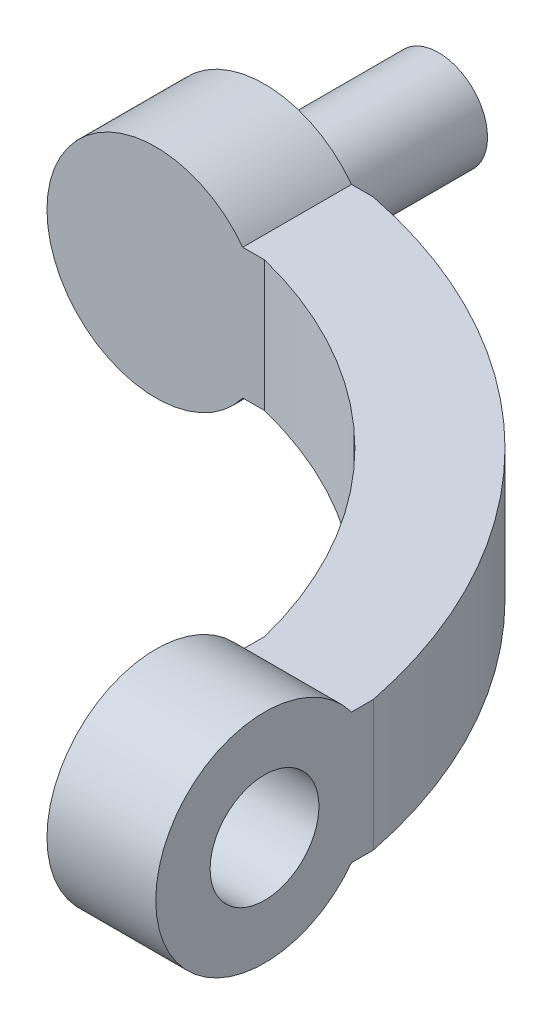
SolidWorks part; units mm, degrees
ref_plane "前视基准面" through (0, 0, 0) normal (0, 0, 1) x (1, 0, 0)
ref_plane "上视基准面" through (0, 0, 0) normal (0, 1, 0) x (1, 0, 0)
ref_plane "右视基准面" through (0, 0, 0) normal (1, 0, 0) x (0, 0, -1)
other "Configuration Table"
sketch "草图2" plane through (0, 0, 0) normal (0, 0, 1) x (1, 0, 0)
  circle A0 centre (0, 0) radius 5
  dimension "D1" = 10
extrude "凸台-拉伸3" add sketch "草图2" along normal blind 5
sketch "草图3" plane through (0, 0, 0) normal (0, 1, 0) x (1, 0, 0)
  line L0 (0, 0) -> (0, -25) construction
  line L1 (0, -25) -> (21.1976, -25) construction
  line L3 (0, 0) -> (5, 0)
  line L4 (0, 0) -> (0, -5)
  line L5 (0, -5) -> (5, -5)
  line L6 (5, 0) -> (5, -5)
  line L7 (20, -20) -> (25, -20)
  line L8 (20, -20) -> (20, -25)
  line L9 (20, -25) -> (25, -25)
  line L10 (25, -20) -> (25, -25)
  arc A0 (5, -5) -> (20, -20) centre (0, -25) cw
  arc A1 (5, 0) -> (25, -20) centre (0, -25) cw
  dimension "D1" = 20
  dimension "D2" = 5
  dimension "D3" = 5
extrude "凸台-拉伸4" add sketch "草图3" along normal blind 3 and the other way blind 3 separate body contours A1 L6 A0 L7 region at (15.52, 0, 9.48)
revolve "旋转1" add sketch "草图3<3>" angle 360 about L1 region at (22.5, 0, 22.5)
sketch "草图3<3>" plane through (0, 0, 0) normal (0, 1, 0) x (1, 0, 0) same geometry as "草图3"
sketch "草图4" plane through (0, 0, 20) normal (0, 0, 1) x (1, 0, 0)
  line L4 (25, 3) -> (20, 3)
  line L5 (20, 3) -> (20, -3)
  line L6 (20, -3) -> (25, -3)
  line L7 (25, -3) -> (25, 3)
  line L8 (25, 3) -> (20, 3)
  line L9 (20, 3) -> (20, -3)
  line L10 (20, -3) -> (25, -3)
  line L11 (25, -3) -> (25, 3)
  dimension "D1" = 0
extrude "凸台-拉伸5" add sketch "草图4" along normal blind 3
sketch "草图5" plane through (5, 0, 0) normal (-1, 0, 0) x (0, 0, 1)
  line L4 (5, -3) -> (5, 3)
  line L5 (5, 3) -> (0, 3)
  line L6 (0, 3) -> (0, -3)
  line L7 (0, -3) -> (5, -3)
  line L8 (5, -3) -> (5, 3)
  line L9 (5, 3) -> (0, 3)
  line L10 (0, 3) -> (0, -3)
  line L11 (0, -3) -> (5, -3)
  dimension "D1" = 0
extrude "凸台-拉伸6" add sketch "草图5" along normal blind 3
sketch "草图6" plane through (20, 0, 0) normal (-1, 0, 0) x (0, 0, 1)
  circle A0 centre (25, 0) radius 2.5
  dimension "D1" = 5
extrude "切除-拉伸1" cut sketch "草图6" against normal blind 5
sketch "草图7" plane through (0, 0, 5) normal (0, 0, 1) x (1, 0, 0)
  circle A0 centre (0, 0) radius 2.25
  dimension "D1" = 4.5
extrude "凸台-拉伸7" add sketch "草图7" against normal blind 8 from surface starting at face at (2.25, 0, 0)
